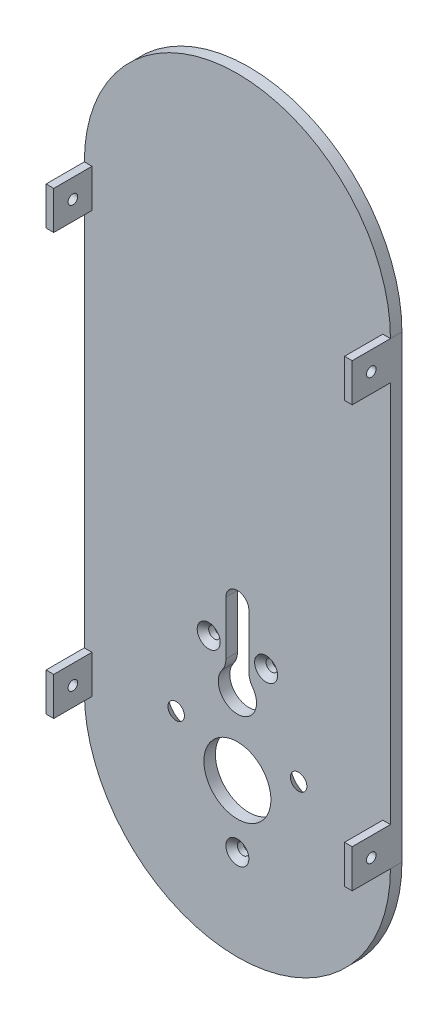
SolidWorks part; units mm, degrees
ref_plane "Front Plane" through (0, 0, 0) normal (0, 0, 1) x (1, 0, 0)
ref_plane "Top Plane" through (0, 0, 0) normal (0, 1, 0) x (1, 0, 0)
ref_plane "Right Plane" through (0, 0, 0) normal (1, 0, 0) x (0, 0, -1)
sketch "Sketch3" plane through (0, 0, 0) normal (0, 0, 1) x (1, 0, 0)
  line L1 (-40, 0) -> (40, 0)
  line L2 (-40, 0) -> (-40, 150)
  line L3 (-30, 160) -> (30, 160)
  line L4 (40, 0) -> (40, 150)
  circle A0 centre (0, 0) radius 40
  arc A1 (30, 160) -> (40, 150) centre (30, 150) cw
  arc A2 (-40, 150) -> (-30, 160) centre (-30, 150) cw
  circle A3 centre (0, 120) radius 40
  point P11 (-40, 160)
  dimension "D2" = 80
  dimension "D4" = 10
  dimension "D5" = 40
  dimension "D6" = 120
  dimension "D1" = 160
  dimension "D3" = 80
extrude "Boss-Extrude4" add sketch "Sketch3" along normal blind 3 contours L1 A0 | L1 A0 | A3 L2 A0 L4 | A3 region at (0, 16.9765, 0) region at (0, 60, 0) region at (0, -16.9765, 0) region at (0, 120, 0)
sketch "Sketch6" plane through (0, 0, 0) normal (0, 0, -1) x (-1, 0, 0)
  circle A0 centre (-7.5, 29.0071) radius 1.5
  circle A1 centre (7.5, 29.0071) radius 1.5
  circle A3 centre (0, -16.25) radius 1.5
  circle A4 centre (0, 7) radius 25 construction
  circle A6 centre (0, 0) radius 8.75
  dimension "D3" = 23.25
  dimension "D4" = 15
  dimension "D5" = 7.5
  dimension "D6" = 3
  dimension "D7" = 3
  dimension "D8" = 3
  dimension "D9" = 17.5
  dimension "D10" = 7
  dimension "D11" = 0
  dimension "D1" = 23.25
  dimension "D2" = 23.25
extrude "Cut-Extrude2" cut sketch "Sketch6" against normal through all
chamfer "Chamfer1" distance 1.5 angle 45 3 edges at (-1.5, -16.25, 3) (-9, 29.0071, 3) (6, 29.0071, 3)
sketch "Sketch9" plane through (0, 0, 0) normal (0, 0, -1) x (-1, 0, 0)
  line L0 (3, 40) -> (3, 20)
  line L1 (-3, 40) -> (-3, 20.8535)
  circle A0 centre (0, 20) radius 3
  circle A1 centre (0, 40) radius 3
  circle A2 centre (0, 20) radius 5
  dimension "D1" = 6
  dimension "D2" = 20
  dimension "D3" = 6
  dimension "D5" = 10
  dimension "D4" = 20
sketch "Sketch12" plane through (0, 0, 3) normal (0, 0, 1) x (1, 0, 0)
  line L0 (40, 0) -> (40, 120) construction
  line L1 (40, 120) -> (38, 120)
  line L2 (40, 120) -> (40, 110)
  line L3 (40, 110) -> (38, 110)
  line L4 (38, 120) -> (38, 110)
  line L5 (-40, 0) -> (-40, 120) construction
  line L6 (-40, 120) -> (-38, 120)
  line L7 (-40, 120) -> (-40, 110)
  line L8 (-40, 110) -> (-38, 110)
  line L9 (-38, 120) -> (-38, 110)
  line L11 (-40, 10) -> (-38, 10)
  line L12 (-40, 10) -> (-40, 0)
  line L13 (-40, 0) -> (-38, 0)
  line L14 (-38, 10) -> (-38, 0)
  line L15 (40, 0) -> (38, 0)
  line L16 (40, 0) -> (40, 10)
  line L17 (40, 10) -> (38, 10)
  line L18 (38, 0) -> (38, 10)
  arc A0 (-40, 0) -> (40, 0) centre (0, 0) ccw construction
  dimension "D1" = 10
  dimension "D2" = 10
  dimension "D3" = 110
  dimension "D4" = 110
  dimension "D5" = 2
  dimension "D6" = 2
  dimension "D7" = 2
  dimension "D9" = 10
  dimension "D10" = 2
  dimension "D12" = 10
extrude "Boss-Extrude7" add sketch "Sketch12" along normal blind 10
sketch "Sketch13" plane through (-40, 0, 0) normal (-1, 0, 0) x (0, 0, 1)
  line L1 (13, 120) -> (3, 120) construction
  line L2 (13, 10) -> (13, 0) construction
  line L3 (13, 10) -> (3, 10) construction
  line L4 (3, 120) -> (3, 160) construction
  circle A0 centre (8, 115) radius 1.25
  circle A1 centre (8, 5) radius 1.25
  dimension "D1" = 5
  dimension "D2" = 5
  dimension "D3" = 2.5
  dimension "D4" = 2.5
  dimension "D5" = 5
  dimension "D6" = 5
extrude "Cut-Extrude8" cut sketch "Sketch13" against normal through all
sketch "Sketch14" plane through (0, 0, 0) normal (0, 0, -1) x (-1, 0, 0)
  circle A0 centre (-16, 7.7) radius 2.15
  circle A1 centre (16, 7.7) radius 2.15
  dimension "D1" = 4.3
  dimension "D3" = 32
  dimension "D4" = 16
  dimension "D5" = 7.7
extrude "Cut-Extrude9" cut sketch "Sketch14" against normal through all
chamfer "Chamfer2" distance 3 angle 45 2 edges at (-18.15, 7.7, 0) (13.85, 7.7, 0)
extrude "Cut-Extrude10" cut sketch "Sketch9" against normal through all contours A2 L0 A1 L1 | A1 | A2 A0 | A0 region at (0, 40, 0) region at (0, 31.1765, 0) region at (0, 20, 0) region at (-4.3456, 22.1728, 0)
fillet "Fillet1" radius 5 2 edges at (3, 24, 1.5) (-3, 24, 1.5)
